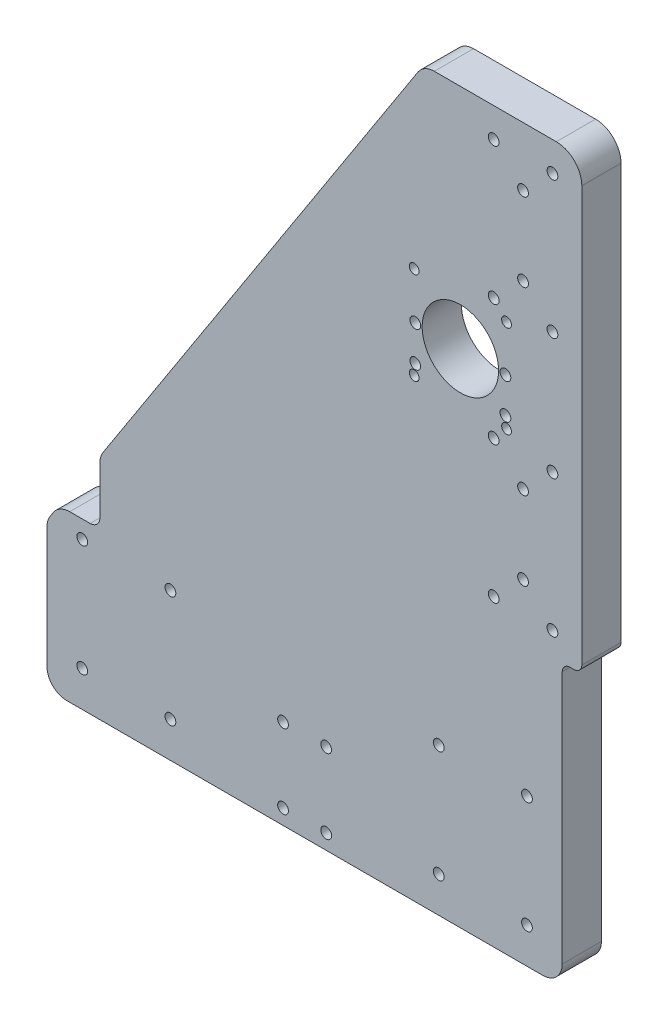
SolidWorks part; units mm, degrees
ref_plane "Front Plane" through (0, 0, 0) normal (0, 0, 1) x (1, 0, 0)
ref_plane "Top Plane" through (0, 0, 0) normal (0, 1, 0) x (1, 0, 0)
ref_plane "Right Plane" through (0, 0, 0) normal (1, 0, 0) x (0, 0, -1)
sketch "Sketch2" plane through (0, 0, 94) normal (0, 0, 1) x (1, 0, 0)
  line L1 (2186.978, 819.9095) -> (2457.8071, 819.9095)
  line L2 (2186.978, 819.9095) -> (2186.978, 457.9095)
  line L3 (2186.978, 457.9095) -> (2457.8071, 457.9095)
  line L4 (2457.8071, 819.9095) -> (2457.8071, 457.9095)
  line L6 (2441.9071, 819.9095) -> (2454.8071, 819.9095) construction
extrude "Boss-Extrude1" add sketch "Sketch2" along normal blind 20
sketch "Sketch3" plane through (0, 0, 114) normal (0, 0, 1) x (1, 0, 0)
  line L0 (2186.978, 819.9095) -> (2186.978, 457.9095) construction
  line L1 (2186.978, 840.163) -> (2194.8071, 840.163)
  line L2 (2186.978, 840.163) -> (2186.978, 445.0092)
  line L3 (2186.978, 445.0092) -> (2194.8071, 445.0092)
  line L4 (2194.8071, 840.163) -> (2194.8071, 445.0092)
extrude "Cut-Extrude1" cut sketch "Sketch3" against normal blind 20
sketch "Sketch4" plane through (0, 0, 114) normal (0, 0, 1) x (1, 0, 0)
  line L0 (2194.8071, 532.657) -> (2380.6092, 819.9095)
  line L1 (2194.8071, 457.9095) -> (2194.8071, 819.9095) construction
  line L2 (2457.8071, 819.9095) -> (2194.8071, 819.9095) construction
  line L3 (2380.6092, 819.9095) -> (2194.8071, 819.9095)
  line L4 (2194.8071, 819.9095) -> (2194.8071, 532.657)
extrude "Cut-Extrude2" cut sketch "Sketch4" against normal blind 20
fillet "Fillet1" radius 10 4 edges at (2457.8071, 457.9095, 104) (2194.8071, 457.9095, 104) (2194.8071, 532.657, 104) (2380.6092, 819.9095, 104)
hole_wizard "M5 Clearance Hole1" positions "Sketch5" profile "Sketch6" hole size "M5" standard "ISO" end condition through all
sketch "Sketch5" plane through (0, 0, 114) normal (0, 0, 1) x (1, 0, 0)
  line L0 (2264.3071, 531.6607) -> (2388.3071, 531.6607) construction
  line L3 (2326.3071, 544.2031) -> (2326.3071, 416.0071) construction
  line L5 (2212.8071, 533.1607) -> (2257.8071, 533.1607) construction
  line L6 (2257.8071, 533.1607) -> (2257.8071, 476.1607) construction
  line L7 (2257.8071, 476.1607) -> (2212.8071, 476.1607) construction
  line L8 (2212.8071, 476.1607) -> (2212.8071, 533.1607) construction
  point P0 (2212.8071, 533.1607)
  point P2 (2257.8071, 533.1607)
  point P4 (2257.8071, 476.1607)
  point P6 (2212.8071, 476.1607)
  point P23 (2439.8071, 476.1607)
  point P24 (2394.8071, 476.1607)
  point P25 (2394.8071, 533.1607)
  point P26 (2439.8071, 533.1607)
  point P27 (2315.3071, 503.6607)
  point P29 (2337.3071, 503.6607)
  point P31 (2315.3071, 465.6607)
  point P33 (2337.3071, 465.6607)
  dimension "D1" = 45
  dimension "D2" = 57
  dimension "D3" = 45
  dimension "D6" = 68.5
  dimension "D7" = 22
  dimension "D8" = 38
  dimension "D9" = 22
  dimension "D10" = 38
  dimension "D11" = 57.5
sketch "Sketch6" plane through (2212.8071, 533.1607, 114) normal (1, 0, 0) x (0, -1, 0)
  line L0 (0, 0) -> (0, 20)
  line L1 (0, 20) -> (2.75, 20)
  line L2 (2.75, 20) -> (2.75, 0)
  line L5 (2.75, 0) -> (0, 0)
  line L11 (0, -6.35) -> (0, 107.95) construction
  dimension "Thru Hole Dia." = 5.5
  dimension "Thru Hole Depth" = 20
fillet "Fillet2" radius 3 1 edges at (2457.8071, 819.9095, 104)
hole_wizard "M5 Clearance Hole2" positions "Sketch7" profile "Sketch8" hole size "M5" standard "ISO" end condition through all
sketch "Sketch7" plane through (0, 0, 114) normal (0, 0, 1) x (1, 0, 0)
  point P0 (2422.8071, 612.9095)
  point P2 (2437.8071, 627.9095)
  point P4 (2452.8071, 612.9095)
  point P6 (2452.8071, 682.9095)
  point P8 (2437.8071, 667.9095)
  point P10 (2422.8071, 682.9095)
  point P12 (2452.8071, 744.9095)
  point P14 (2422.8071, 814.9095)
  point P16 (2452.8071, 814.9095)
  point P18 (2422.8071, 744.9095)
  point P20 (2437.8071, 759.9095)
  point P22 (2437.8071, 799.9095)
sketch "Sketch8" plane through (2422.8071, 612.9095, 114) normal (1, 0, 0) x (0, -1, 0)
  line L0 (0, 0) -> (0, 20)
  line L1 (0, 20) -> (2.75, 20)
  line L2 (2.75, 20) -> (2.75, 0)
  line L5 (2.75, 0) -> (0, 0)
  line L11 (0, -6.35) -> (0, 107.95) construction
  dimension "Thru Hole Dia." = 5.5
  dimension "Thru Hole Depth" = 20
hole_wizard "M5 Clearance Hole3" positions "Sketch9" profile "Sketch10" hole size "M5" standard "ISO" end condition through all
sketch "Sketch9" plane through (0, 0, 94) normal (0, 0, -1) x (-1, 0, 0)
  point P0 (-2428.8071, 713.9095)
  point P2 (-2428.8071, 695.9095)
  point P4 (-2382.8071, 695.9095)
  point P6 (-2382.8071, 713.9095)
sketch "Sketch10" plane through (2428.8071, 713.9095, 94) normal (1, 0, 0) x (0, 1, 0)
  line L0 (0, 0) -> (0, 20)
  line L1 (0, 20) -> (2.75, 20)
  line L2 (2.75, 20) -> (2.75, 0)
  line L5 (2.75, 0) -> (0, 0)
  line L11 (0, -6.35) -> (0, 107.95) construction
  dimension "Thru Hole Dia." = 5.5
  dimension "Thru Hole Depth" = 20
sketch "Sketch11" plane through (0, 0, 114) normal (0, 0, 1) x (1, 0, 0)
  circle A3 centre (2405.8071, 713.9095) radius 19.5
  dimension "D1" = 19.5
extrude "Cut-Extrude4" cut sketch "Sketch11" against normal blind 32.2668
sketch "Sketch12" plane through (0, 0, 114) normal (0, 0, 1) x (1, 0, 0)
  line L10 (2221.8071, 542.1607) -> (2195.8071, 542.1607)
  line L11 (2221.8071, 575.6607) -> (2221.8071, 542.1607)
  line L12 (2221.8071, 575.6607) -> (2195.8071, 542.1607)
  point P8 (2221.8071, 542.1607)
  point P10 (2221.3383, 542.1607)
extrude "Cut-Extrude5" cut sketch "Sketch12" against normal blind 20
fillet "Fillet3" radius 10 2 edges at (2221.8071, 574.3993, 104) (2200.9543, 542.1607, 104)
fillet "Fillet4" radius 5 1 edges at (2221.8071, 542.1607, 104)
hole_wizard "Tap Drill for M6 Tap1" positions "Sketch13" profile "Sketch14" hole size "M6" standard "ISO" end condition through all
sketch "Sketch13" plane through (0, 0, 94) normal (0, 0, -1) x (-1, 0, 0)
  point P0 (-2429.3771, 737.4795)
  point P2 (-2382.2371, 737.4795)
  point P4 (-2429.3771, 690.3395)
  point P6 (-2382.2371, 690.3395)
sketch "Sketch14" plane through (2429.3771, 737.4795, 94) normal (1, 0, 0) x (0, 1, 0)
  line L0 (0, 0) -> (0, 20)
  line L1 (0, 20) -> (2.5, 20)
  line L2 (2.5, 20) -> (2.5, 0)
  line L5 (2.5, 0) -> (0, 0)
  line L11 (0, -6.35) -> (0, 107.95) construction
  dimension "Thru Hole Dia." = 5
  dimension "Thru Hole Depth" = 20
sketch "Sketch15" plane through (0, 0, 114) normal (0, 0, 1) x (1, 0, 0)
  line L0 (2457.8071, 467.9095) -> (2457.8071, 816.9095) construction
  line L1 (2454.8071, 819.9095) -> (2386.0506, 819.9095) construction
  line L2 (2457.8071, 597.1048) -> (2457.8071, 816.9095)
  line L3 (2454.8071, 819.9095) -> (2386.0506, 819.9095)
  line L4 (2467.8071, 605.1048) -> (2467.8071, 816.9095)
  line L5 (2454.8071, 829.9095) -> (2392.5188, 829.9095)
  line L6 (2463.8071, 601.1048) -> (2461.8071, 601.1048)
  line L7 (2223.4105, 576.8782) -> (2377.654, 815.3406) construction
  line L8 (2377.654, 815.3406) -> (2384.1222, 825.3406)
  line L9 (2467.8071, 467.9095) -> (2467.8071, 816.9095) construction
  line L10 (2457.8071, 467.9095) -> (2457.8071, 816.9095) construction
  line L11 (2454.8071, 829.9095) -> (2386.0506, 829.9095) construction
  line L12 (2457.8071, 597.1048) -> (2457.8071, 582.296)
  arc A0 (2386.0506, 819.9095) -> (2377.654, 815.3406) centre (2386.0506, 809.9095) ccw construction
  arc A1 (2457.8071, 816.9095) -> (2454.8071, 819.9095) centre (2454.8071, 816.9095) ccw construction
  arc A2 (2386.0506, 819.9095) -> (2377.654, 815.3406) centre (2386.0506, 809.9095) ccw
  arc A3 (2457.8071, 816.9095) -> (2454.8071, 819.9095) centre (2454.8071, 816.9095) ccw
  arc A4 (2467.8071, 816.9095) -> (2454.8071, 829.9095) centre (2454.8071, 816.9095) ccw
  arc A5 (2463.8071, 601.1048) -> (2467.8071, 605.1048) centre (2463.8071, 605.1048) ccw
  arc A6 (2386.0506, 829.9095) -> (2369.2574, 820.7718) centre (2386.0506, 809.9095) ccw construction
  arc A7 (2457.8071, 597.1048) -> (2461.8071, 601.1048) centre (2461.8071, 597.1048) cw
  arc A8 (2384.1222, 825.3406) -> (2392.5188, 829.9095) centre (2392.5188, 819.9095) cw
  point P26 (0, 0)
  line M54 (2457.8071, 467.9095) -> (2457.8071, 816.9095)
  arc M55 (2457.8071, 816.9095) -> (2454.8071, 819.9095) centre (2454.8071, 816.9095) ccw
  line M56 (2454.8071, 819.9095) -> (2386.0506, 819.9095)
  arc M57 (2386.0506, 819.9095) -> (2377.654, 815.3406) centre (2386.0506, 809.9095) ccw
  dimension "D2" = 4
  dimension "D3" = 10
  dimension "D1" = 10
extrude "Boss-Extrude2" add sketch "Sketch15" against normal blind 20 contours A8 L8 A7 L6 A5 L4 A4 L5 M57 M56 M55 M54 region at (2460.3036, 707.0072, 114)
